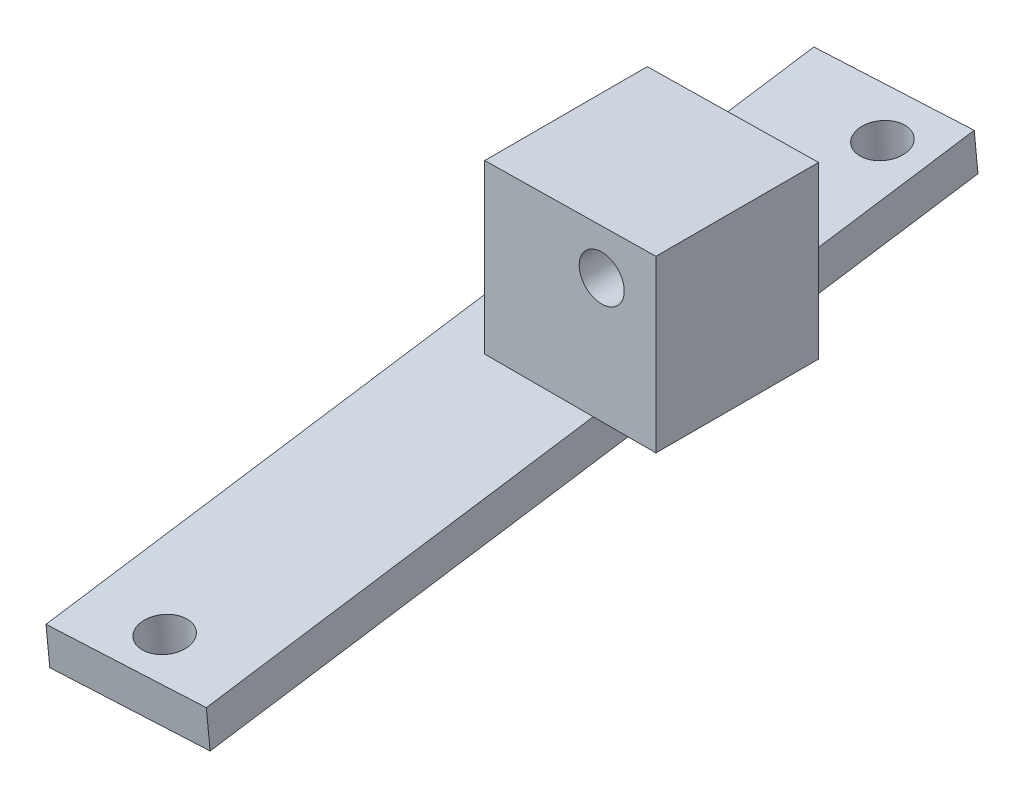
SolidWorks part; units mm, degrees
ref_plane "Front Plane" through (0, 0, 0) normal (0, 0, 1) x (1, 0, 0)
ref_plane "Top Plane" through (0, 0, 0) normal (0, 1, 0) x (1, 0, 0)
ref_plane "Right Plane" through (0, 0, 0) normal (1, 0, 0) x (0, 0, -1)
sketch "Sketch1" plane through (0, 0, 0) normal (0, 0, 1) x (1, 0, 0)
  line L4 (-277.3561, 264.2791) -> (-301.4861, 263.9)
  line L5 (-301.4861, 263.9) -> (-301.4861, 241.3438)
  line L6 (-301.4861, 241.3438) -> (-277.3561, 241.7228)
  line L7 (-277.3561, 241.7228) -> (-277.3561, 264.2791)
  circle A0 centre (-285, 257.8082) radius 3.175
  dimension "D6" = 6.35
  dimension "D1" = 3.81
  dimension "D2" = 3.81
  dimension "D3" = 24.13
  dimension "D4" = 22.5535
  dimension "D5" = 6.35
extrude "Boss-Extrude3" add sketch "Sketch1" along normal up to surface (22.9108 mm away) contours L7 L4 L5 L6 | A0
ref_plane "Plane1" through (0, 240.2331, 23.0373) normal (0, 0.9954, 0.0955) x (1, 0, 0)
sketch "Sketch2" plane through (0, 240.2331, 23.0373) normal (0, 0.9954, 0.0955) x (1, 0, 0)
  line L0 (-310.494, 55.7739) -> (-305.0454, -58.3962)
  line L1 (-305.0454, -58.3962) -> (-283.48, -57.367)
  line L2 (-283.48, -57.367) -> (-288.9285, 56.8031)
  line L3 (-288.9285, 56.8031) -> (-310.494, 55.7739)
  line L4 (-301.4861, 23.0381) -> (-277.3561, 23.0743) construction
  circle A0 centre (-294.8214, 49.7285) radius 3.175
  circle A1 centre (-294.8214, -51.8715) radius 3.175
  point P11 (-294.8214, 49.7285)
  point P13 (-296.017, -13.5103)
  point P14 (-294.8214, -51.8715)
  dimension "D9" = 6.35
  dimension "D10" = 6.35
  dimension "D1" = 87.354
  dimension "D2" = 21.59
  dimension "D3" = 6.35
  dimension "D4" = 58.3918
  dimension "D5" = 114.3
extrude "Boss-Extrude4" add sketch "Sketch2" against normal blind 5.588
sketch "Sketch5" plane through (0, 0, 22.9108) normal (0, 0, 1) x (1, 0, 0)
  line L0 (-301.4861, 241.3438) -> (-301.4861, 240.2807)
  line L1 (-301.4861, 240.2807) -> (-277.3561, 240.2807)
  line L2 (-277.3561, 240.2807) -> (-277.3561, 241.7228)
  line L3 (-277.3561, 241.7228) -> (-301.4861, 241.3438)
extrude "Boss-Extrude5" add sketch "Sketch5" against normal up to surface (22.9108 mm away) up to face at (-288.7208, 249.3921, 0)
